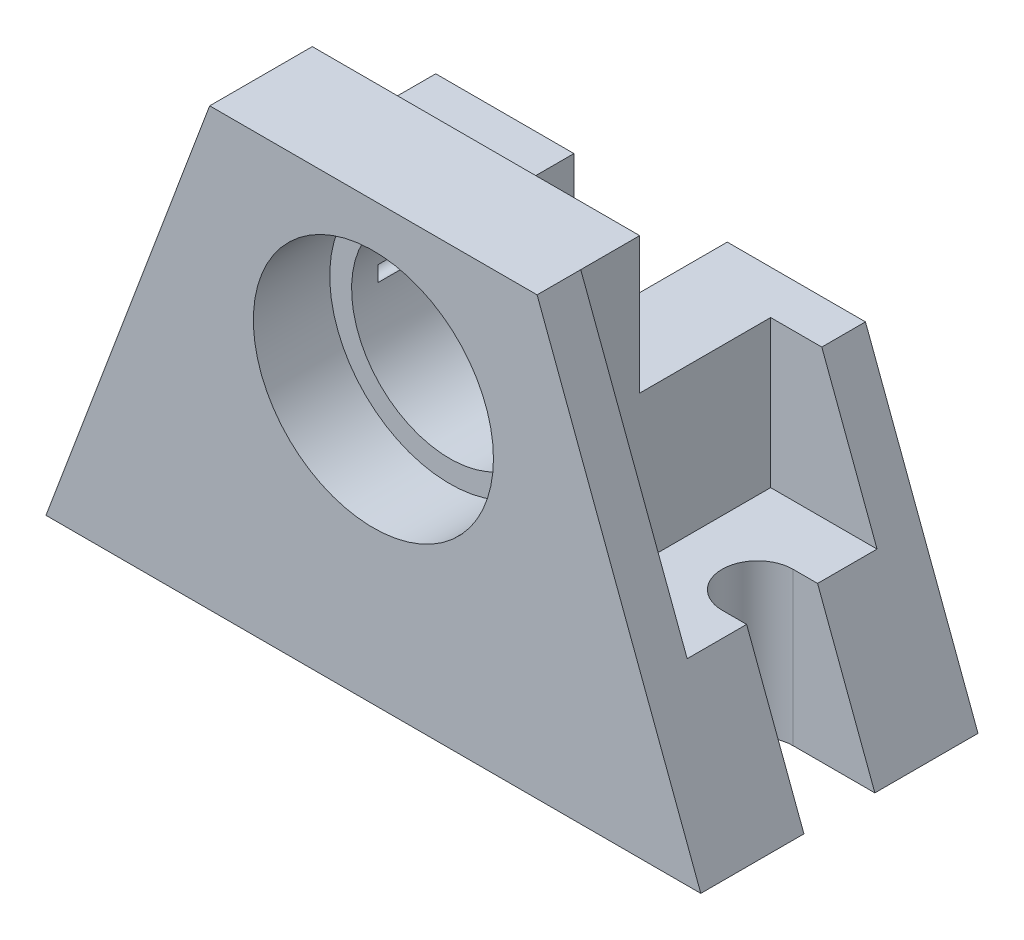
SolidWorks part; units mm, degrees
ref_plane "Front Plane" through (0, 0, 0) normal (0, 0, 1) x (1, 0, 0)
ref_plane "Top Plane" through (0, 0, 0) normal (0, 1, 0) x (1, 0, 0)
ref_plane "Right Plane" through (0, 0, 0) normal (1, 0, 0) x (0, 0, -1)
sketch "Sketch3" plane through (0, 0, 0) normal (0, 0, 1) x (1, 0, 0)
  line L0 (-30, -25) -> (30, -25)
  line L1 (30, -25) -> (15, 15)
  line L2 (15, 15) -> (-15, 15)
  line L3 (-15, 15) -> (-30, -25)
  line L4 (0, 15) -> (0, -25) construction
  circle A0 centre (0, 0) radius 9
  point P8 (0, 0)
  point P10 (0, 0)
  dimension "D4" = 18
  dimension "D1" = 30
  dimension "D2" = 40
  dimension "D3" = 60
  dimension "D5" = 25
extrude "Boss-Extrude3" add sketch "Sketch3" along normal blind 25.4
sketch "Sketch4" plane through (0, 15, 0) normal (0, 1, 0) x (1, 0, 0)
  line L0 (0, -25.4) -> (0, 0) construction
  line L1 (15, -25.4) -> (-15, -25.4) construction
  line L3 (30, -21.4) -> (12, -21.4)
  line L4 (-30, -21.4) -> (30, -21.4) construction
  line L5 (-30, -21.4) -> (-30, -4) construction
  line L6 (-30, -4) -> (30, -4) construction
  line L7 (30, -21.4) -> (30, -4) construction
  line L8 (-30, -21.4) -> (30, -4) construction
  line L9 (-30, -4) -> (30, -21.4) construction
  line L14 (30, -21.4) -> (30, -4)
  line L19 (15, 0) -> (-15, 0) construction
  line L20 (30, -25.4) -> (30, 0) construction
  line L21 (30, -4) -> (12, -4)
  line L22 (12, -21.4) -> (12, -4)
  line L23 (-30, -21.4) -> (-12, -21.4)
  line L24 (-30, -21.4) -> (-30, -4)
  line L25 (-30, -4) -> (-12, -4)
  line L26 (-12, -21.4) -> (-12, -4)
  point P6 (0, -12.7)
  line M4 (-15, 0) -> (-15, -25.4)
  line M6 (15, -25.4) -> (15, 0)
  dimension "D1" = 4
  dimension "D2" = 18
  dimension "D3" = 4
  dimension "D4" = 18
extrude "Cut-Extrude2" cut sketch "Sketch4" against normal blind 26 contours L4 M4 | L14 L21 L3 M6 | L4 L7 L6 L5 region at (22.5, 15, 12.7) region at (-22.5, 15, 12.7)
sketch "Sketch5" plane through (0, 0, 0) normal (0, 0, -1) x (-1, 0, 0)
  line L0 (-9.525, 0) -> (9.525, 0) construction
  line L1 (-9.525, 8.7666) -> (-9.525, -11) construction
  line L3 (9.525, 8.4673) -> (9.525, -11) construction
  line L4 (-12.025, 2.5) -> (-12.025, -25)
  line L5 (-12.025, 2.5) -> (-7.025, 2.5)
  line L6 (-12.025, -25) -> (-7.025, -25)
  line L7 (-7.025, 2.5) -> (-7.025, -25)
  line L8 (-12.025, 2.5) -> (-7.025, -25) construction
  line L9 (-12.025, -25) -> (-7.025, 2.5) construction
  line L10 (7.025, 2.5) -> (7.025, -25)
  line L11 (7.025, 2.5) -> (12.025, 2.5)
  line L12 (7.025, -25) -> (12.025, -25)
  line L13 (12.025, 2.5) -> (12.025, -25)
  line L14 (7.025, 2.5) -> (12.025, -25) construction
  line L15 (7.025, -25) -> (12.025, 2.5) construction
  line L18 (30, -25) -> (-30, -25) construction
  circle A0 centre (9.525, 0) radius 0.9
  circle A1 centre (-9.525, 0) radius 0.9
  point P3 (0, 0)
  point P14 (-9.525, -11.25)
  point P15 (9.525, -11.25)
  dimension "D2" = 1.8
  dimension "D3" = 1.8
  dimension "D1" = 19.05
  dimension "D4" = 5
  dimension "D5" = 5
  dimension "D6" = 2.5
extrude "Boss-Extrude4" add sketch "Sketch5" against normal blind 10 contours L10 L12 L13 L11 | L7 L6 L4 L5
sketch "Sketch6" plane through (0, 0, 0) normal (0, 0, -1) x (-1, 0, 0)
  line L0 (7.025, 2.5) -> (8.6458, 2.5) construction
  line L1 (-30, 2.5) -> (30, 2.5)
  line L2 (-30, 2.5) -> (-30, 15)
  line L3 (-30, 15) -> (30, 15)
  line L4 (30, 2.5) -> (30, 15)
  line L6 (-15, 15) -> (15, 15) construction
extrude "Cut-Extrude3" cut sketch "Sketch6" against normal blind 16
sketch "Sketch7" plane through (0, -25, 0) normal (0, -1, 0) x (1, 0, 0)
  line L0 (0, 0) -> (0, 25.4) construction
  line L5 (12.5, 9.45) -> (-12.5, 9.45)
  line L6 (12.5, 9.45) -> (12.5, 15.95)
  line L7 (12.5, 15.95) -> (-12.5, 15.95)
  line L8 (-12.5, 9.45) -> (-12.5, 15.95)
  line L9 (-30, 25.4) -> (30, 25.4) construction
  line L10 (30, 12.7) -> (-30, 12.7) construction
  line L11 (30, 25.4) -> (30, 0) construction
  line L12 (-30, 25.4) -> (-30, 0) construction
  point P9 (0, 9.45)
  point P16 (-12.5, 12.7)
  dimension "D1" = 6.5
  dimension "D2" = 25
extrude "Boss-Extrude5" add sketch "Sketch7" along normal blind 4
sketch "Sketch8" plane through (0, -25, 0) normal (0, -1, 0) x (1, 0, 0)
  line L0 (30, 12.7) -> (-30, 12.7) construction
  line L1 (30, 25.4) -> (30, 0) construction
  line L2 (-30, 25.4) -> (-30, 0) construction
  line L3 (-37.5, 12.7) -> (-22.5, 12.7) construction
  line L4 (37.5, 12.7) -> (22.5, 12.7) construction
  line L5 (37.5, 9.45) -> (22.5, 9.45)
  line L6 (37.5, 15.95) -> (22.5, 15.95)
  line L7 (-37.5, 15.95) -> (-22.5, 15.95)
  line L8 (-37.5, 9.45) -> (-22.5, 9.45)
  arc A0 (37.5, 9.45) -> (37.5, 15.95) centre (37.5, 12.7) ccw
  arc A1 (22.5, 15.95) -> (22.5, 9.45) centre (22.5, 12.7) ccw
  arc A2 (-37.5, 15.95) -> (-37.5, 9.45) centre (-37.5, 12.7) ccw
  arc A3 (-22.5, 9.45) -> (-22.5, 15.95) centre (-22.5, 12.7) ccw
  point P10 (30, 12.7)
  point P16 (-30, 12.7)
  dimension "D1" = 6.5
  dimension "D2" = 7.5
  dimension "D3" = 6.5
  dimension "D4" = 7.5
extrude "Cut-Extrude4" cut sketch "Sketch8" against normal through all
sketch "Sketch9" plane through (0, 0, 25.4) normal (0, 0, 1) x (1, 0, 0)
  circle A0 centre (0, 0) radius 11
  dimension "D1" = 22
extrude "Cut-Extrude5" cut sketch "Sketch9" against normal blind 7
extrude "Cut-Extrude6" cut sketch "Sketch5<3>" against normal up to surface (16 mm away) contours A0 | A1 up to face at (0, 7.75, 16)
sketch "Sketch5<3>" plane through (0, 0, 0) normal (0, 0, -1) x (-1, 0, 0) same geometry as "Sketch5"
